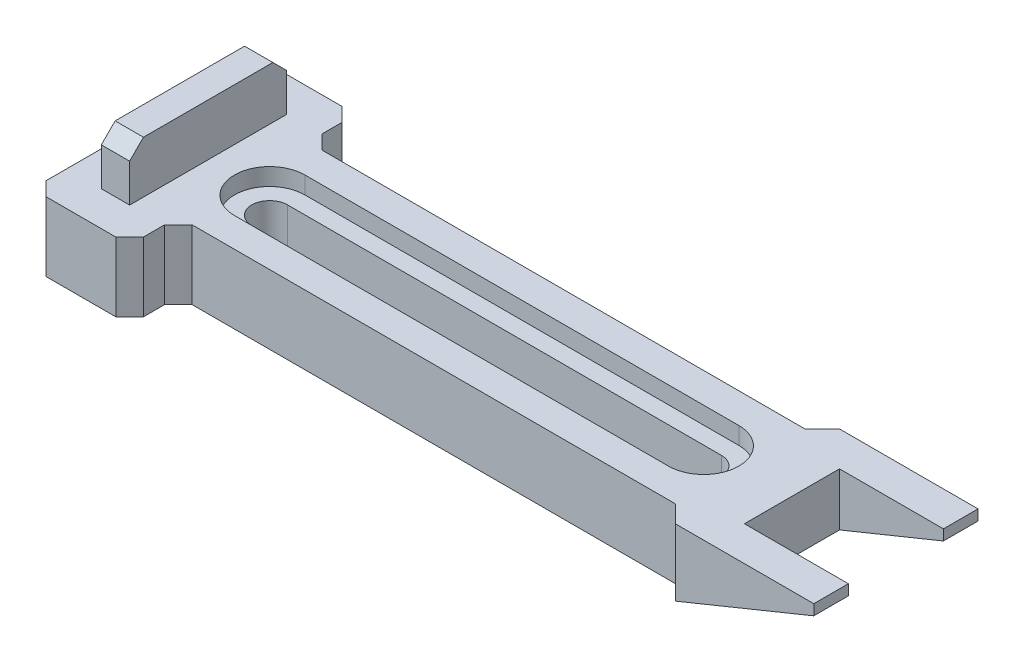
SolidWorks part; units mm, degrees
ref_plane "Front Plane" through (0, 0, 0) normal (0, 0, 1) x (1, 0, 0)
ref_plane "Top Plane" through (0, 0, 0) normal (0, 1, 0) x (1, 0, 0)
ref_plane "Right Plane" through (0, 0, 0) normal (1, 0, 0) x (0, 0, -1)
sketch "Sketch1" plane through (0, 0, 0) normal (0, 1, 0) x (1, 0, 0)
  line L0 (-26.0741, -28.2158) -> (-26.0741, -42.3104)
  line L1 (-54.2632, 23.1286) -> (-26.0741, 23.1286)
  line L2 (-54.2632, 23.1286) -> (-54.2632, -42.3104)
  line L3 (-54.2632, -42.3104) -> (-26.0741, -42.3104)
  line L4 (-26.0741, 23.1286) -> (-26.0741, 9.2858)
  line L5 (-26.0741, 9.2858) -> (122.6737, 9.2858)
  line L7 (-26.0741, -28.2158) -> (122.6737, -28.2158)
  line L8 (122.6737, 9.2858) -> (122.6737, -28.2158)
extrude "Boss-Extrude1" add sketch "Sketch1" along normal blind 20 contours L7 L8 L5 L4 L1 L2 L3 L0
sketch "Sketch2" plane through (0, 20, 0) normal (0, 1, 0) x (1, 0, 0)
  line L0 (-18.2805, -9.5909) -> (107.2568, -9.5909) construction
  line L1 (-18.2805, 0.5849) -> (107.2568, 0.5849)
  line L2 (-18.2805, -19.7667) -> (107.2568, -19.7667)
  line L3 (-18.2805, -4.4151) -> (107.2568, -4.4151)
  line L4 (-18.2805, -14.7667) -> (107.2568, -14.7667)
  arc A0 (-18.2805, 0.5849) -> (-18.2805, -19.7667) centre (-18.2805, -9.5909) ccw
  arc A1 (107.2568, -19.7667) -> (107.2568, 0.5849) centre (107.2568, -9.5909) ccw
  arc A2 (107.2568, -14.7667) -> (107.2568, -4.4151) centre (107.2568, -9.5909) ccw
  arc A3 (-18.2805, -4.4151) -> (-18.2805, -14.7667) centre (-18.2805, -9.5909) ccw
  point P2 (44.4882, -9.5909)
  dimension "D1" = 5
extrude "Cut-Extrude1" cut sketch "Sketch2" against normal blind 5
sketch "Sketch3" plane through (0, 20, 0) normal (0, 1, 0) x (1, 0, 0)
  line L9 (-18.2805, -14.7667) -> (107.2568, -14.7667)
  line L10 (107.2568, -4.4151) -> (-18.2805, -4.4151)
  line L11 (-18.2805, -14.7667) -> (107.2568, -14.7667)
  line L12 (107.2568, -4.4151) -> (-18.2805, -4.4151)
  arc A5 (107.2568, -14.7667) -> (107.2568, -4.4151) centre (107.2568, -9.5909) ccw
  arc A6 (-18.2805, -4.4151) -> (-18.2805, -14.7667) centre (-18.2805, -9.5909) ccw
  arc A7 (107.2568, -14.7667) -> (107.2568, -4.4151) centre (107.2568, -9.5909) ccw
  arc A8 (-18.2805, -4.4151) -> (-18.2805, -14.7667) centre (-18.2805, -9.5909) ccw
  dimension "D2" = 10.3516
  dimension "D1" = 0
extrude "Cut-Extrude2" cut sketch "Sketch3" against normal through all
chamfer "Chamfer1" distance 4 angle 45 6 edges at (-26.0741, 10, -9.2858) (-26.0741, 10, 28.2158) (-26.0741, 10, 42.3104) (-26.0741, 10, -23.1286) (-54.2632, 10, -23.1286) (-54.2632, 10, 42.3104)
sketch "Sketch4" plane through (0, 20, 0) normal (0, 1, 0) x (1, 0, 0)
  line L14 (-33.1452, 12.0575) -> (-34.2163, 13.1286)
  line L15 (-34.2163, 13.1286) -> (-44.2632, 13.1286)
  line L16 (-44.2632, 13.1286) -> (-44.2632, 13.1286)
  line L17 (-44.2632, 13.1286) -> (-44.2632, -32.3104)
  line L18 (-44.2632, -32.3104) -> (-44.2632, -32.3104)
  line L19 (-44.2632, -32.3104) -> (-36.0741, -32.3104)
  line L20 (-36.0741, -32.3104) -> (-36.0741, -32.3104)
  line L21 (-36.0741, -32.3104) -> (-36.0741, -32.2158)
  line L22 (-36.0741, -32.3104) -> (-36.0741, 13.1286)
  line L28 (-50.2632, -42.3104) -> (-30.0741, -42.3104)
  line L29 (-30.0741, -42.3104) -> (-26.0741, -38.3104)
  line L30 (-26.0741, -38.3104) -> (-26.0741, -32.2158)
  line L31 (-26.0741, -32.2158) -> (-22.0741, -28.2158)
  line L32 (-22.0741, -28.2158) -> (122.6737, -28.2158)
  line L33 (122.6737, -28.2158) -> (122.6737, 9.2858)
  line L34 (122.6737, 9.2858) -> (-22.0741, 9.2858)
  line L35 (-22.0741, 9.2858) -> (-26.0741, 13.2858)
  line L36 (-26.0741, 13.2858) -> (-26.0741, 19.1286)
  line L37 (-26.0741, 19.1286) -> (-30.0741, 23.1286)
  line L38 (-30.0741, 23.1286) -> (-50.2632, 23.1286)
  line L39 (-50.2632, 23.1286) -> (-54.2632, 19.1286)
  line L40 (-54.2632, 19.1286) -> (-54.2632, -38.3104)
  line L41 (-54.2632, -38.3104) -> (-50.2632, -42.3104)
  line L42 (-50.2632, -42.3104) -> (-30.0741, -42.3104)
  line L43 (-30.0741, -42.3104) -> (-26.0741, -38.3104)
  line L44 (-26.0741, -38.3104) -> (-26.0741, -32.2158)
  line L45 (-26.0741, -32.2158) -> (-22.0741, -28.2158)
  line L46 (-22.0741, -28.2158) -> (122.6737, -28.2158)
  line L47 (122.6737, -28.2158) -> (122.6737, 9.2858)
  line L48 (122.6737, 9.2858) -> (-22.0741, 9.2858)
  line L49 (-22.0741, 9.2858) -> (-26.0741, 13.2858)
  line L50 (-26.0741, 13.2858) -> (-26.0741, 19.1286)
  line L51 (-26.0741, 19.1286) -> (-30.0741, 23.1286)
  line L52 (-30.0741, 23.1286) -> (-50.2632, 23.1286)
  line L53 (-50.2632, 23.1286) -> (-54.2632, 19.1286)
  line L54 (-54.2632, 19.1286) -> (-54.2632, -38.3104)
  line L55 (-54.2632, -38.3104) -> (-50.2632, -42.3104)
  dimension "D1" = 0
  dimension "D2" = 10
extrude "Boss-Extrude2" add sketch "Sketch4" along normal blind 15 contours L21 L22 L15 L17 L19 region at (-40.1687, 20, 9.5909)
chamfer "Chamfer2" distance 4 angle 45 2 edges at (-40.1687, 35, -13.1286) (-40.1687, 35, 32.3104)
sketch "Sketch5" plane through (0, 20, 0) normal (0, 1, 0) x (1, 0, 0)
  line L3 (122.6737, -33.2158) -> (162.7356, -33.2158)
  line L4 (122.6737, -33.2158) -> (122.6737, 14.2858)
  line L5 (122.6737, 14.2858) -> (162.7356, 14.2858)
  line L7 (132.6737, -23.2158) -> (162.7356, -23.2158)
  line L8 (132.6737, -23.2158) -> (132.6737, 4.2858)
  line L9 (132.6737, 4.2858) -> (162.7356, 4.2858)
  line L11 (162.7356, 14.2858) -> (162.7356, 4.2858)
  line L12 (162.7356, -23.2158) -> (162.7356, -33.2158)
  dimension "D1" = 10
  dimension "D2" = 10
  dimension "D3" = 10
extrude "Boss-Extrude3" add sketch "Sketch5" against normal up to surface (20 mm away) contours L9 L11 L5 L4 L3 L12 L7 L8 up to face at (44.4882, 0, 9.5909)
chamfer "Chamfer3" distance 5 angle 45 2 edges at (122.6737, 10, -9.2858) (122.6737, 10, 28.2158)
sketch "Sketch6" plane through (0, 0, 33.2158) normal (0, 0, 1) x (1, 0, 0)
  line L8 (120.8004, -0.1533) -> (162.7356, 16.9539)
  line L10 (120.8004, -0.1533) -> (162.7356, 0)
  line L11 (162.7356, 0) -> (162.7356, 16.9539)
extrude "Cut-Extrude3" cut sketch "Sketch6" against normal blind 60
scale "Scale2" scale about centroid uniform scaling yes scale factor 0.19
